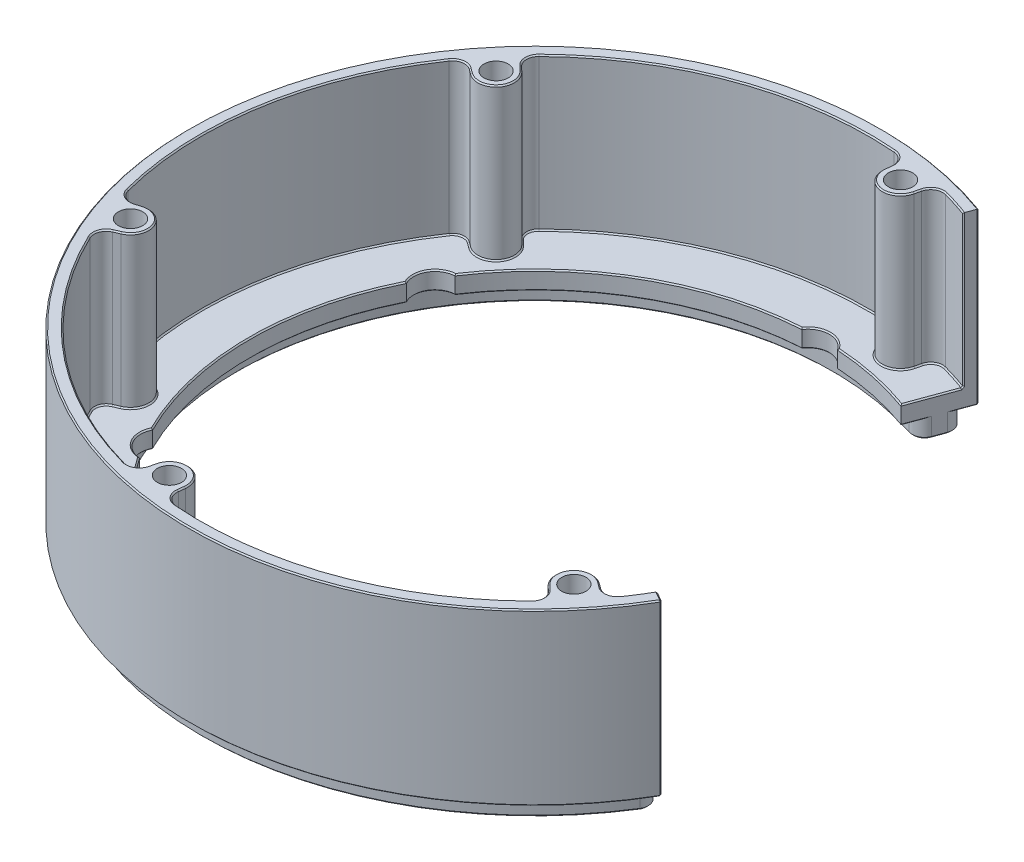
SolidWorks part; units mm, degrees
note: The reader was unsure of these and kept them because the rebuilt part matched: shared geometry of "스케치7<5>", "스케치7<6>".
material "6061-T6 (SS)"
ref_plane "정면" through (0, 0, 0) normal (0, 0, 1) x (1, 0, 0)
ref_plane "윗면" through (0, 0, 0) normal (0, 1, 0) x (1, 0, 0)
ref_plane "우측면" through (0, 0, 0) normal (1, 0, 0) x (0, 0, -1)
sketch "스케치1" plane through (0, 0, 0) normal (0, 1, 0) x (1, 0, 0)
  line L0 (0, 0) -> (350, 0) construction
  line L1 (0, 45) -> (0, 0) construction
  line L2 (0, 0) -> (38.9711, 22.5) construction
  line L3 (71.0141, -16) -> (350, -16)
  line L4 (350, -14) -> (71.0141, -14)
  line L5 (350, 32) -> (350, 40) construction
  line L6 (350, 16) -> (46.3141, 16) construction
  line L7 (350, 40) -> (40.6079, 40) construction
  line L8 (169.6004, 50) -> (28.1957, 50)
  line L9 (170, 52) -> (28.1957, 52)
  line L10 (80, -11) -> (180, -11) construction
  line L11 (0, 32) -> (350, 32) construction
  line L12 (0, 45) -> (0, 0) construction
  line L13 (0, 0) -> (-39.8343, 33.425) construction
  line L14 (-39.8343, 33.425) -> (0, 0) construction
  line L15 (0, 0) -> (-52, 0) construction
  line L16 (55, 47) -> (155, 47) construction
  line L17 (-39.8343, 33.425) -> (0, 0) construction
  line L18 (0, 0) -> (9.0297, 51.21) construction
  circle A18 centre (0, 0) radius 41
  circle A19 centre (350, 0) radius 6
  circle A25 centre (0, 0) radius 45
  circle A26 centre (0, 0) radius 49
  circle A28 centre (0, 45) radius 2.1
  circle A33 centre (0, 45) radius 3.5
  circle A34 centre (38.9711, 22.5) radius 2.1
  circle A36 centre (38.9711, 22.5) radius 3.5
  circle A37 centre (38.9711, -22.5) radius 2.1
  circle A38 centre (38.9711, -22.5) radius 3.5
  circle A40 centre (0, -45) radius 2.1
  circle A41 centre (0, -45) radius 3.5
  circle A42 centre (-38.9711, -22.5) radius 2.1
  circle A44 centre (-38.9711, -22.5) radius 3.5
  circle A45 centre (-38.9711, 22.5) radius 2.1
  circle A46 centre (-38.9711, 22.5) radius 3.5
  circle A48 centre (350, 0) radius 14
  arc A49 (322.2872, -16) -> (322.7607, 16.7934) centre (350, 0) ccw
  circle A50 centre (0, 0) radius 32
  arc A52 (350, -16) -> (342.254, -14) centre (350, 0) ccw
  arc A60 (170, 52) -> (350, 16) centre (350, 484) ccw
  arc A61 (169.6004, 50) -> (350, 14) centre (350, 484) ccw
  arc A75 (19.5995, 53.5244) -> (49.3634, -28.5) centre (0, 0) ccw
  arc A110 (71.0141, -16) -> (49.3634, -28.5) centre (71.0141, -41) ccw
  arc A111 (71.0141, -14) -> (47.6314, -27.5) centre (71.0141, -41) ccw
  circle A114 centre (0, 0) radius 55
  circle A130 centre (0, 0) radius 52
  circle A131 centre (55, 47) radius 2.1
  circle A142 centre (-39.8343, 33.425) radius 2.1
  circle A143 centre (9.0297, 51.21) radius 2.1
  circle A145 centre (39.8343, -33.425) radius 2.1
  circle A146 centre (-9.0297, -51.21) radius 2.1
  arc A147 (19.5995, 53.5244) -> (28.1957, 52) centre (28.1957, 77) ccw
  arc A148 (18.9118, 51.6463) -> (28.1957, 50) centre (28.1957, 77) ccw
  arc A149 (53.0537, -20.84) -> (27.3679, 50) centre (0, 0) ccw
  circle A152 centre (80, -11) radius 2.1
  circle A161 centre (130, -11) radius 2.1
  circle A165 centre (180, -11) radius 2.1
  circle A168 centre (105, 47) radius 2.1
  circle A172 centre (230, -11) radius 2.1
  circle A177 centre (155, 47) radius 2.1
  circle A180 centre (0, 0) radius 57
  circle A181 centre (-48.864, -17.785) radius 2.1
  circle A182 centre (48.864, 17.785) radius 2.1
  point P29 (0, 0)
  point P57 (-0.5, 0.2887)
  point P59 (0, 0)
  point P73 (0, 0)
  point P120 (0, 0)
  point P168 (0, 0)
  point P170 (0, 0)
  point P171 (0, 0)
  dimension "D2" = 82
  dimension "D3" = 90
  dimension "D4" = 98
  dimension "D7" = 7
  dimension "D8" = 60
  dimension "D10" = 28
  dimension "D11" = 64
  dimension "D12" = 64
  dimension "D13" = 32
  dimension "D14" = 60
  dimension "D19" = 50
  dimension "D21" = 50
  dimension "D17" = 180
  dimension "D20" = 3
  dimension "D22" = 8
  dimension "D23" = 2
  dimension "D25" = 50
  dimension "D26" = 4.2
  dimension "D28" = 80
  dimension "D32" = 3
  dimension "D33" = 50
  dimension "D35" = 4
  dimension "D5" = 114
  dimension "D6" = 4.2
  dimension "D9" = 12
  dimension "D18" = 6
  dimension "D16" = 104
  dimension "D27" = 4.2
  dimension "D37" = 25
  dimension "D15" = 4.2
  dimension "D1" = 350
  dimension "D34" = 6
  dimension "D38" = 50
  dimension "D24" = 10
  dimension "D30" = 3
sketch "스케치2" plane through (0, 0, 0) normal (0, 1, 0) x (1, 0, 0)
  circle A10 centre (350, 0) radius 6.25
  circle A11 centre (382.6753, 12.5429) radius 10
  arc A12 (390.9123, -1.174) -> (378.5037, 27.9895) centre (382.6753, 12.5429) ccw
  arc A13 (231.9844, -40.1605) -> (80.8156, -91.5048) centre (227.4834, -275.1173) ccw
  arc A14 (357.0381, -19.254) -> (358.9138, -18.4606) centre (350, 0) ccw
  arc A15 (358.9138, -18.4606) -> (390.9123, -1.174) centre (184.9867, 341.7468) ccw
  arc A16 (231.9844, -40.1605) -> (357.0381, -19.254) centre (238.5923, 304.7763) ccw
  arc A17 (378.5037, 27.9895) -> (343.7427, 16.8774) centre (482.7931, -358.1759) ccw
  arc A18 (233.0814, -9.5331) -> (343.3893, 16.7421) centre (196.4849, 388.7893) ccw
  arc A19 (233.0814, -9.5331) -> (41.3157, -82.3545) centre (261.5552, -373.4208) ccw
sketch "스케치3" plane through (0, 0, 0) normal (0, 1, 0) x (1, 0, 0)
  line L0 (350, -2.1721) -> (350, 87.1857) construction
  line L1 (350, 32) -> (0, 32) construction
  line L2 (350, 36) -> (-50.8808, 36) construction
  line L3 (350, 28) -> (-10.04, 28) construction
  circle A0 centre (356.8277, -1.9267) radius 6.25
  circle A1 centre (350, 32) radius 10
  arc A2 (365.7576, 37.7743) -> (333.8887, 36.6981) centre (350, 32) ccw
  arc A3 (345.2, -124.5693) -> (338.96, -284.0977) centre (562.9381, -212.9724) ccw
  arc A4 (377.1409, -4.6879) -> (376.6334, 3.3632) centre (356.8277, -1.9267) ccw
  arc A5 (376.6334, 3.3632) -> (365.7576, 37.7743) centre (-9.8202, -99.853) ccw
  arc A6 (345.2, -124.5693) -> (377.1409, -4.6879) centre (-114.7569, 62.1762) ccw
  arc A7 (333.8887, 36.6981) -> (325.3353, 1.5106) centre (717.8951, -75.28) ccw
  arc A8 (317, -112.5693) -> (332.0008, -0.1718) centre (-67.981, -3.9891) ccw
  arc A9 (317, -112.5693) -> (316.262, -317.6949) centre (666.9225, -216.3924) ccw
  dimension "D1" = 4
  dimension "D2" = 4
sketch "스케치5" plane through (0, 0, 0) normal (0, -1, 0) x (1, 0, 0)
  line L0 (-13.4586, 50.2281) -> (0, 0) construction
  line L1 (0, 0) -> (36.7696, 36.7696) construction
  line L2 (0, 0) -> (0, 50.2281) construction
  circle A0 centre (-13.4586, 50.2281) radius 3.5
  circle A1 centre (36.7696, 36.7696) radius 3.5
  circle A3 centre (13.4586, -50.2281) radius 3.5
  circle A4 centre (-36.7696, -36.7696) radius 3.5
  circle A5 centre (-50.2281, 13.4586) radius 3.5
  circle A6 centre (50.2281, -13.4586) radius 3.5 [skipped]
  point P15 (0, 0)
  dimension "D1" = 7
  dimension "D3" = 60
  dimension "D4" = 45
  dimension "D5" = 52
  dimension "D2" = 6
sketch "스케치7" plane through (0, 0, 0) normal (0, 1, 0) x (1, 0, 0)
  line L0 (0, 0) -> (19.5995, 53.5244) construction
  line L1 (0, 0) -> (49.3634, -28.5) construction
  line L2 (19.5995, 53.5244) -> (16.161, 44.1341)
  line L3 (49.3634, -28.5) -> (40.7032, -23.5)
  line L4 (0, 0) -> (6.1724, 52.6013) construction
  line L5 (6.1724, 52.6013) -> (6.0501, 51.5596)
  line L6 (0, 0) -> (12.1906, 51.5402) construction
  line L7 (12.1906, 51.5402) -> (11.9492, 50.5195)
  line L8 (48.6403, 20.9552) -> (47.677, 20.5402)
  line L9 (50.7304, 15.2127) -> (49.7257, 14.9115)
  line L10 (42.4679, -31.6461) -> (41.6269, -31.0194)
  line L11 (38.5398, -36.3274) -> (37.7766, -35.608)
  line L12 (-6.1724, -52.6013) -> (-6.0501, -51.5596)
  line L13 (-12.1906, -51.5402) -> (-11.9492, -50.5195)
  line L14 (-48.6403, -20.9552) -> (-47.677, -20.5402)
  line L15 (-50.7304, -15.2127) -> (-49.7257, -14.9115)
  line L16 (-42.4679, 31.6461) -> (-41.6269, 31.0194)
  line L17 (-38.5398, 36.3274) -> (-37.7766, 35.608)
  circle A0 centre (0, 0) radius 57
  circle A1 centre (0, 0) radius 49
  circle A2 centre (0, 0) radius 55
  circle A3 centre (9.0297, 51.21) radius 2
  circle A4 centre (48.864, 17.785) radius 2
  circle A5 centre (39.8343, -33.425) radius 2
  circle A6 centre (-9.0297, -51.21) radius 2
  circle A7 centre (-48.864, -17.785) radius 2
  circle A8 centre (-39.8343, 33.425) radius 2
  circle A9 centre (0, 0) radius 52 construction
  circle A10 centre (0, 0) radius 47
  arc A11 (6.0501, 51.5596) -> (11.9492, 50.5195) centre (9.0297, 51.21) ccw
  arc A12 (6.1724, 52.6013) -> (4.344, 54.8282) centre (4.186, 52.8344) ccw
  arc A13 (14.6703, 53.0074) -> (12.1906, 51.5402) centre (14.1369, 51.0798) ccw
  arc A14 (48.6403, 20.9552) -> (49.6546, 23.6521) centre (47.849, 22.792) ccw
  arc A15 (47.677, 20.5402) -> (49.7257, 14.9115) centre (48.864, 17.785) ccw
  arc A16 (53.2409, 13.7988) -> (50.7304, 15.2127) centre (51.3049, 13.297) ccw
  arc A17 (42.4679, -31.6461) -> (45.3106, -31.1761) centre (43.663, -30.0424) ccw
  arc A18 (41.6269, -31.0194) -> (37.7766, -35.608) centre (39.8343, -33.425) ccw
  arc A19 (38.5706, -39.2086) -> (38.5398, -36.3274) centre (37.168, -37.7828) ccw
  arc A20 (-6.1724, -52.6013) -> (-4.344, -54.8282) centre (-4.186, -52.8344) ccw
  arc A21 (-6.0501, -51.5596) -> (-11.9492, -50.5195) centre (-9.0297, -51.21) ccw
  arc A22 (-14.6703, -53.0074) -> (-12.1906, -51.5402) centre (-14.1369, -51.0798) ccw
  arc A23 (-48.6403, -20.9552) -> (-49.6546, -23.6521) centre (-47.849, -22.792) ccw
  arc A24 (-47.677, -20.5402) -> (-49.7257, -14.9115) centre (-48.864, -17.785) ccw
  arc A25 (-53.2409, -13.7988) -> (-50.7304, -15.2127) centre (-51.3049, -13.297) ccw
  arc A26 (-42.4679, 31.6461) -> (-45.3106, 31.1761) centre (-43.663, 30.0424) ccw
  arc A27 (-41.6269, 31.0194) -> (-37.7766, 35.608) centre (-39.8343, 33.425) ccw
  arc A28 (-38.5706, 39.2086) -> (-38.5398, 36.3274) centre (-37.168, 37.7828) ccw
  arc A29 (44.1333, -25.4804) -> (41.4418, -26.1453) centre (43.1333, -27.2124) ccw
  arc A30 (46.5597, -29.2778) -> (45.8667, -26.4811) centre (44.8667, -28.2132) ccw
  arc A31 (18.2111, 49.7328) -> (16.9494, 52.3232) centre (16.333, 50.4205) ccw
  arc A32 (15.0313, 46.6375) -> (17.5229, 47.8534) centre (15.6448, 48.5411) ccw
  point P21 (0, 0)
  point P87 (0, 0)
  dimension "D1" = 114
  dimension "D2" = 110
  dimension "D3" = 98
  dimension "D4" = 4
  dimension "D6" = 94
  dimension "D7" = 4
  dimension "D9" = 4
  dimension "D10" = 4
  dimension "D5" = 6
  dimension "D8" = 6
extrude "보스-돌출1" add sketch "스케치7" along normal blind 28 contours A2 L2 A0 L3 | A28 A2 A26 L16 A27 L17 A8 | A13 A2 A12 L5 A11 L7 A3 | A25 A2 A23 L14 A24 L15 A7 | A22 A2 A20 L12 A21 L13 A6 | A19 A2 A17 L10 A18 L11 A5
extrude "보스-돌출2" add sketch "스케치7<5>" along normal blind 3 contours A2 A28 L17 A27 A1 A11 L5 A12 | A10 L2 A1 L3 | A27 L16 A26 A2 A25 L15 A24 A1 | A2 A13 L7 A11 A1 L2 | A24 L14 A23 A2 A22 L13 A21 A1 | A21 L12 A20 A2 A19 L11 A18 A1 | A18 L10 A17 A2 L3 A1 | A31 L2 A2 | A32 A1 L2 | A29 L3 A1 | A30 A2 L3
sketch "스케치7<5>" plane through (0, 0, 0) normal (0, 1, 0) x (1, 0, 0) same geometry as "스케치7"
extrude "보스-돌출3" add sketch "스케치7<6>" against normal blind 3 contours A2 A13 L7 A11 A1 L2 | A13 A2 A12 L5 A11 L7 A3 | A2 A28 L17 A27 A1 A11 L5 A12 | A28 A2 A26 L16 A27 L17 A8 | A27 L16 A26 A2 A25 L15 A24 A1 | A25 A2 A23 L14 A24 L15 A7 | A24 L14 A23 A2 A22 L13 A21 A1 | A22 A2 A20 L12 A21 L13 A6 | A21 L12 A20 A2 A19 L11 A18 A1 | A19 A2 A17 L10 A18 L11 A5 | A18 L10 A17 A2 L3 A1
sketch "스케치7<6>" plane through (0, 0, 0) normal (0, 1, 0) x (1, 0, 0) same geometry as "스케치7"
sketch "스케치8" plane through (0, 0, 0) normal (0, 1, 0) x (1, 0, 0)
  circle A0 centre (0, 0) radius 45
  circle A1 centre (0, 45) radius 3.5
  circle A2 centre (38.9711, 22.5) radius 3.5
  circle A3 centre (38.9711, -22.5) radius 3.5
  circle A4 centre (0, -45) radius 3.5
  circle A5 centre (-38.9711, -22.5) radius 3.5
  circle A6 centre (-38.9711, 22.5) radius 3.5
  point P17 (0, 0)
  dimension "D1" = 90
  dimension "D2" = 7
  dimension "D3" = 6
extrude "컷-돌출1" cut sketch "스케치8" along normal blind 10 contours A0 A6 | A0 A6 | A0 A1 | A0 A1 | A0 A3 | A0 A3 | A0 A4 | A0 A4 | A0 A5 | A0 A5
chamfer "모따기1" distance 0.3 angle 45 8 edges at (42.6537, -3, 25.2708) (45, -3, 25.9808) (46.8079, -3, 27.7321) (-46.0612, -3, 16.7141) (16.522, -3, -46.7437) (-51.7014, -3, 18.7607) (17.867, -3, -48.7931) (18.1311, -3, -51.2963)
chamfer "모따기2" distance 0.2 angle 45 95 edges at (18.9118, 15.5, -51.6463) (17.5364, 3, -47.8902) (9.6477, 3, -45.9991) (9.6477, 0, -45.9991) (0, 3, -48.5) (0, 0, -48.5) (-23.5, 0, -40.7032) (-23.5, 3, -40.7032) (-42.0022, 3, -24.25) (-42.0022, 0, -24.25) (-47, 3, 0) (-47, 0, 0) (-42.0022, 3, 24.25) (-42.0022, 0, 24.25) (-23.5, 3, 40.7032) (-23.5, 0, 40.7032) (0, 3, 48.5) (0, 0, 48.5) (23.5, 3, 40.7032) (23.5, 0, 40.7032) (40.801, 0, 25.4836) (40.801, 3, 25.4836) (44.8168, 3, 25.875) (47.6314, 15.5, 27.5) (43.0678, 0, 24.8652) (16.8419, 0, -45.9938) (47.6151, 0, 27.4906) (18.9053, 0, -51.6286) (19.5995, 14, -53.5244) (-53.5814, 0, 19.443) (-53.5814, 28, 19.443) (49.3634, 14, 28.5) (16.8048, 28, -52.3698) (16.8048, 3, -52.3698) (13.1184, 3, -52.8011) (13.1184, 28, -52.8011) (12.0699, 3, -51.0298) (12.0699, 28, -51.0298) (8.5088, 3, -48.2556) (8.5088, 28, -48.2556) (6.1113, 3, -52.0805) (6.1113, 28, -52.0805) (5.7317, 3, -54.1036) (5.7317, 28, -54.1036) (-18.8111, 28, -51.6831) (-18.8111, 3, -51.6831) (-39.1679, 3, -37.7615) (-39.1679, 28, -37.7615) (-38.1582, 3, -35.9677) (-38.1582, 28, -35.9677) (-37.5362, 3, -31.4966) (-37.5362, 28, -31.4966) (-42.0474, 3, -31.3328) (-42.0474, 28, -31.3328) (-43.9892, 3, -32.0156) (-43.9892, 28, -32.0156) (-54.1644, 28, -9.5506) (-54.1644, 3, -9.5506) (-52.2863, 3, 15.0396) (-52.2863, 28, 15.0396) (-50.2281, 3, 15.0621) (-50.2281, 28, 15.0621) (-46.0449, 3, 16.759) (-46.0449, 28, 16.759) (-48.1587, 3, 20.7477) (-48.1587, 28, 20.7477) (-49.7209, 3, 22.088) (-49.7209, 28, 22.088) (-35.3533, 28, 42.1324) (-35.3533, 3, 42.1324) (-13.1184, 3, 52.8011) (-13.1184, 28, 52.8011) (-12.0699, 3, 51.0298) (-12.0699, 28, 51.0298) (-8.5088, 3, 48.2556) (-8.5088, 28, 48.2556) (-6.1113, 3, 52.0805) (-6.1113, 28, 52.0805) (-5.7317, 3, 54.1036) (-5.7317, 28, 54.1036) (18.8111, 28, 51.6831) (18.8111, 3, 51.6831) (39.1679, 3, 37.7615) (39.1679, 28, 37.7615) (38.1582, 3, 35.9677) (38.1582, 28, 35.9677) (37.5362, 3, 31.4966) (37.5362, 28, 31.4966) (42.0474, 3, 31.3328) (42.0474, 28, 31.3328) (43.9892, 3, 32.0156) (43.9892, 28, 32.0156) (46.5073, 28, 29.361) (46.5073, 3, 29.361) (48.4974, 28, 28)
